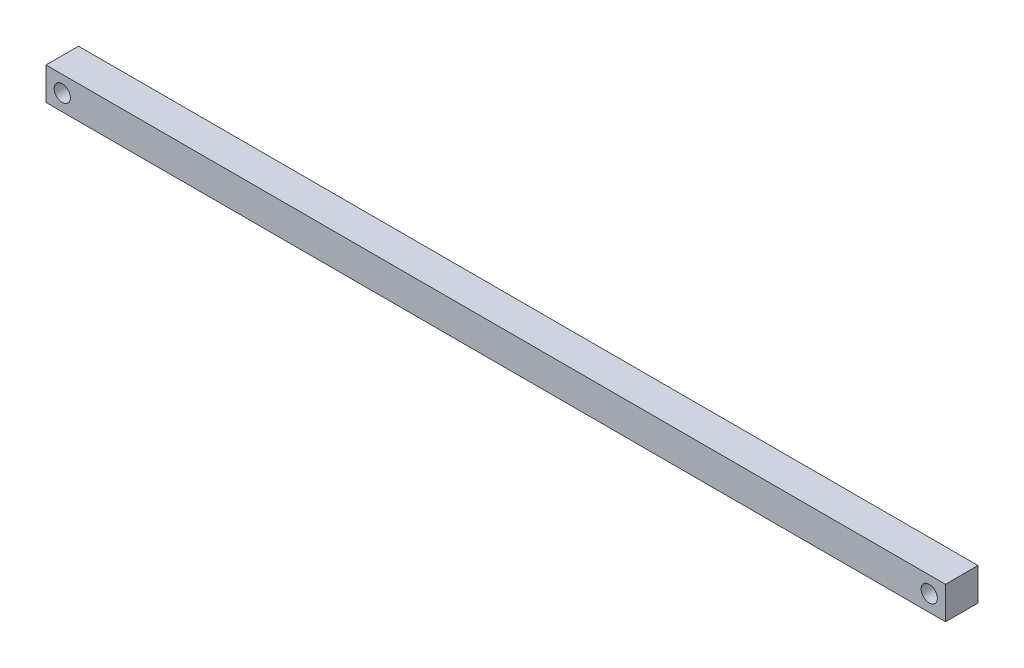
SolidWorks part; units mm, degrees
ref_plane "Front Plane" through (0, 0, 0) normal (0, 0, 1) x (1, 0, 0)
ref_plane "Top Plane" through (0, 0, 0) normal (0, 1, 0) x (1, 0, 0)
ref_plane "Right Plane" through (0, 0, 0) normal (1, 0, 0) x (0, 0, -1)
sketch "Sketch1" plane through (0, 0, 0) normal (0, 0, 1) x (1, 0, 0)
  line L0 (400, 0) -> (-400, 0) construction
  line L1 (415, 15) -> (-415, 15)
  line L2 (415, 15) -> (415, -15)
  line L3 (415, -15) -> (-415, -15)
  line L4 (-415, 15) -> (-415, -15)
  line L5 (415, 15) -> (-415, -15) construction
  line L6 (415, -15) -> (-415, 15) construction
  circle A0 centre (-400, 0) radius 7.5
  circle A1 centre (400, 0) radius 7.5
  point P0 (0, 0)
  point P8 (0, 0)
  dimension "D2" = 15
  dimension "D1" = 30
  dimension "D3" = 800
  dimension "D4" = 15
extrude "Boss-Extrude1" add sketch "Sketch1" along normal mid plane 30
equation "\"A\"= 200"
equation "\"hole_diameter\"=15"
equation "\"D2@Sketch1\"=\"hole_diameter\""
equation "\"D3@Sketch1\"=4*\"A\""
equation "\"D4@Sketch1\"=\"hole_diameter\""
